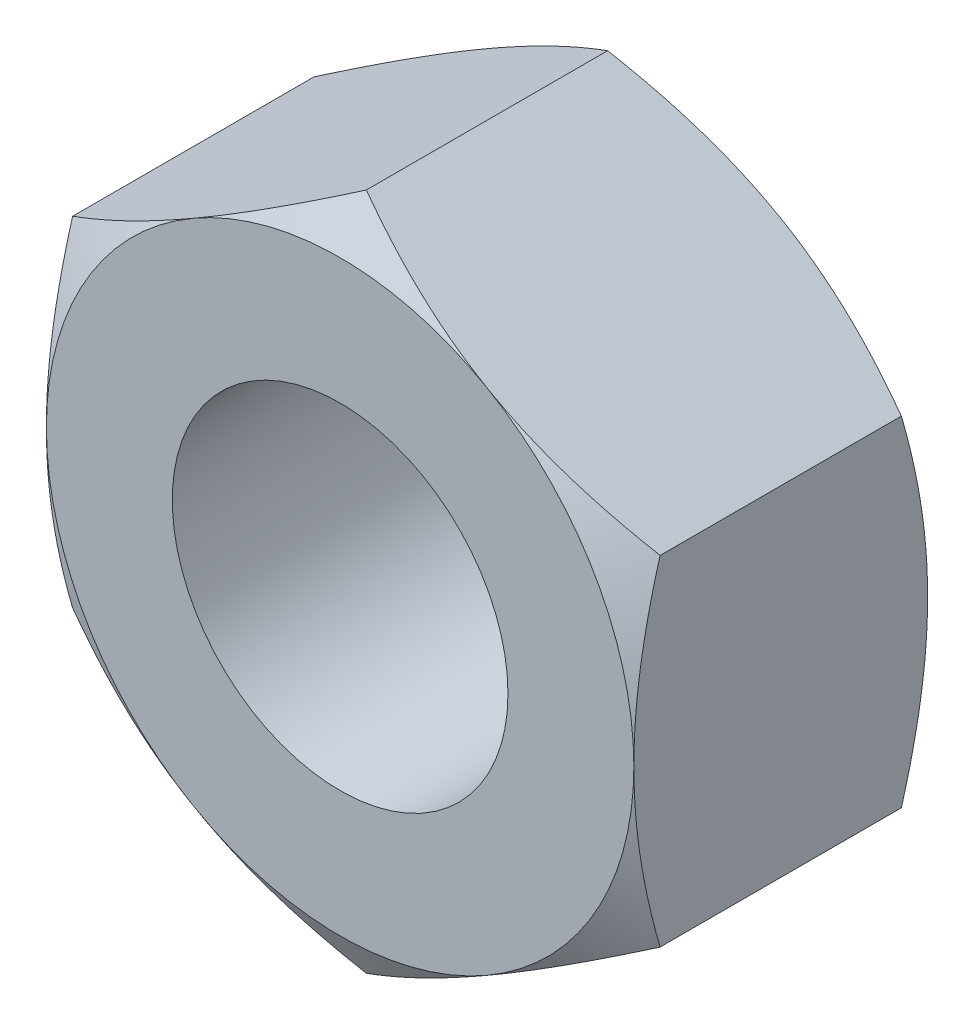
SolidWorks part; units mm, degrees
ref_plane "Front" through (0, 0, 0) normal (0, 0, 1) x (1, 0, 0)
ref_plane "Top" through (0, 0, 0) normal (0, 1, 0) x (1, 0, 0)
ref_plane "Right" through (0, 0, 0) normal (1, 0, 0) x (0, 0, -1)
sketch "Sketch1" plane through (0, 0, 0) normal (0, 0, 1) x (1, 0, 0)
  line L1 (-5.5562, 3.2079) -> (-5.5562, -3.2079)
  line L2 (-5.5562, -3.2079) -> (0, -6.4158)
  line L3 (0, -6.4158) -> (5.5562, -3.2079)
  line L4 (5.5562, -3.2079) -> (5.5562, 3.2079)
  line L5 (5.5562, 3.2079) -> (0, 6.4158)
  line L6 (0, 6.4158) -> (-5.5562, 3.2079)
  circle A0 centre (0, 0) radius 5.5562 construction
  circle A1 centre (0, 0) radius 3.175
  point P10 (0, 3.175)
  dimension "hex" = 11.1125
  dimension "dia" = 6.35
extrude "Extrude1" add sketch "Sketch1" along normal mid plane 5.5562
sketch "Sketch4" plane through (0, 0, -2.7781) normal (0, 0, -1) x (-1, 0, 0)
  circle A0 centre (0, 0) radius 3.175 construction
  circle A1 centre (0, 0) radius 3.175
curve "Helix/Spiral3" [suppressed] pitch 1.27 height 6.6675 turns 5.25
sketch "Sketch3" plane through (0, 0, 0) normal (1, 0, 0) x (0, 0, -1)
  line L0 (2.7781, 3.175) -> (3.8894, 3.175)
  line L1 (3.8894, 3.175) -> (3.4131, 2.3501)
  line L2 (3.4131, 2.3501) -> (3.2544, 2.3501)
  line L3 (3.2544, 2.3501) -> (2.7781, 3.175)
  line L4 (3.0163, 2.7626) -> (3.6513, 2.7626) construction
  dimension "D1" = 60
  dimension "D2" = 0.635
  dimension "D3" = 0.1588
sweep "Sweep1" [suppressed] add profiles "Sketch3" path "Helix/Spiral3"
sketch "Sketch6" [suppressed] plane through (0, 0, 0) normal (1, 0, 0) x (0, 0, -1)
  line L0 (-3.0956, 3.4925) -> (-2.4606, 2.8575)
  line L1 (-2.4606, 2.8575) -> (-2.4606, 0) construction
  line L2 (3.9291, 0) -> (-3.9291, 0) construction
  line L3 (-2.4606, 0) -> (-3.8894, 0)
  line L4 (-3.8894, 0) -> (-3.8894, 3.4925)
  line L5 (-3.8894, 3.4925) -> (-3.0956, 3.4925)
  line L6 (-2.4606, 2.8575) -> (0.3969, 0)
  line L7 (0.3969, 0) -> (-2.4606, 0)
  line L8 (-2.7781, -3.2079) -> (-2.7781, 3.2079) construction
  point P2 (-2.7781, 3.175)
  dimension "D2" = 0.635
  dimension "D1" = 45
revolve "Cut-Revolve1" [suppressed] cut sketch "Sketch6" angle 360 about L3
sketch "Sketch7" plane through (0, 0, 2.7781) normal (0, 0, 1) x (1, 0, 0)
  circle A0 centre (0, 0) radius 5.5562 construction
  circle A1 centre (0, 0) radius 5.5562
extrude "Extrude2" cut sketch "Sketch7" against normal blind 25.4 draft 60 flip side to cut
mirror "Mirror1" about plane through (0, 0, 0) normal (0, 0, 1) of "Extrude2", "Cut-Revolve1"
sketch "Sketch8" [suppressed] plane through (0, 0, 2.7781) normal (0, 0, 1) x (1, 0, 0)
  line L0 (-2.2451, 2.2451) -> (0, 0) construction
  line L1 (0, -3.9291) -> (0, 3.9291) construction
  circle A0 centre (0, 0) radius 3.175 construction
  point P0 (-2.2451, 2.2451)
  dimension "D1" = 45
ref_axis "Axis1" through (0, 0, 3.0559) along (0, 0, -1)
equation "\"D3@Helix/Spiral3\" = \"length@Extrude1\" * 1.2"
equation "\"D2@Sketch3\" = \"D4@Helix/Spiral3\" * .5"
equation "\"D3@Sketch3\" = \"D4@Helix/Spiral3\" * .125"
equation "\"D2@Sketch6\" = \"D4@Helix/Spiral3\" * .5"
